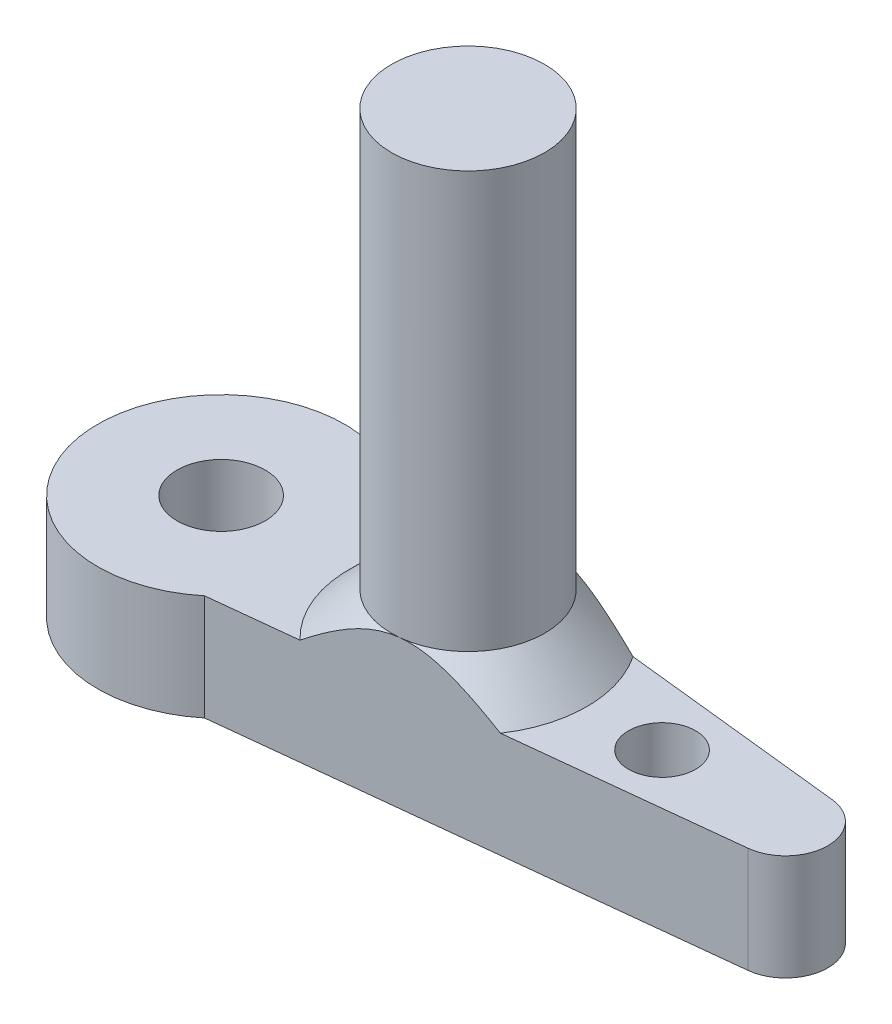
SolidWorks part; units mm, degrees
ref_plane "Front Plane" through (0, 0, 0) normal (0, 0, 1) x (1, 0, 0)
ref_plane "Top Plane" through (0, 0, 0) normal (0, 1, 0) x (1, 0, 0)
ref_plane "Right Plane" through (0, 0, 0) normal (1, 0, 0) x (0, 0, -1)
sketch "Sketch1" plane through (0, 0, 0) normal (0, 1, 0) x (1, 0, 0)
  line L0 (-2.2271, 2.7) -> (-16.1293, 1.193)
  line L1 (-2.2271, -2.7) -> (-16.1293, -1.193)
  line L2 (0, 0) -> (0, 7.2501) construction
  line L3 (2.2271, -2.7) -> (16.1293, -1.193)
  line L4 (2.2271, 2.7) -> (16.1293, 1.193)
  line L5 (6, 2.291) -> (6, -2.291)
  circle A0 centre (0, 0) radius 2.5
  circle A1 centre (0, 0) radius 3.5
  circle A2 centre (-16, 0) radius 1.2
  circle A3 centre (16, 0) radius 1.2
  circle A4 centre (-12.5, 0) radius 0.95
  circle A5 centre (12.5, 0) radius 0.95
  circle A6 centre (8.5, 0) radius 1
  circle A7 centre (0, 0) radius 1.25
  dimension "D1" = 5
  dimension "D2" = 7
  dimension "D3" = 2.4
  dimension "D4" = 2.4
  dimension "D8" = 12.5
  dimension "D9" = 1.9
  dimension "D11" = 2
  dimension "D13" = 2.5
  dimension "D5" = 32
  dimension "D6" = 16
  dimension "D7" = 5.4
  dimension "D10" = 6
  dimension "D12" = 4
extrude "Boss-Extrude1" add sketch "Sketch1" along normal blind 3
sketch "Sketch2" plane through (0, 3, 0) normal (0, 1, 0) x (1, 0, 0)
  line L1 (2.2271, 2.7) -> (16.1293, 1.193) construction
  circle A0 centre (7, 0) radius 2.1699
  dimension "D2" = 7
extrude "Boss-Extrude2" add sketch "Sketch2" along normal blind 13
chamfer "Chamfer1" distance 1.2 angle 45 2 edges at (4.8301, 3, 0) (9.1699, 3, 0)
